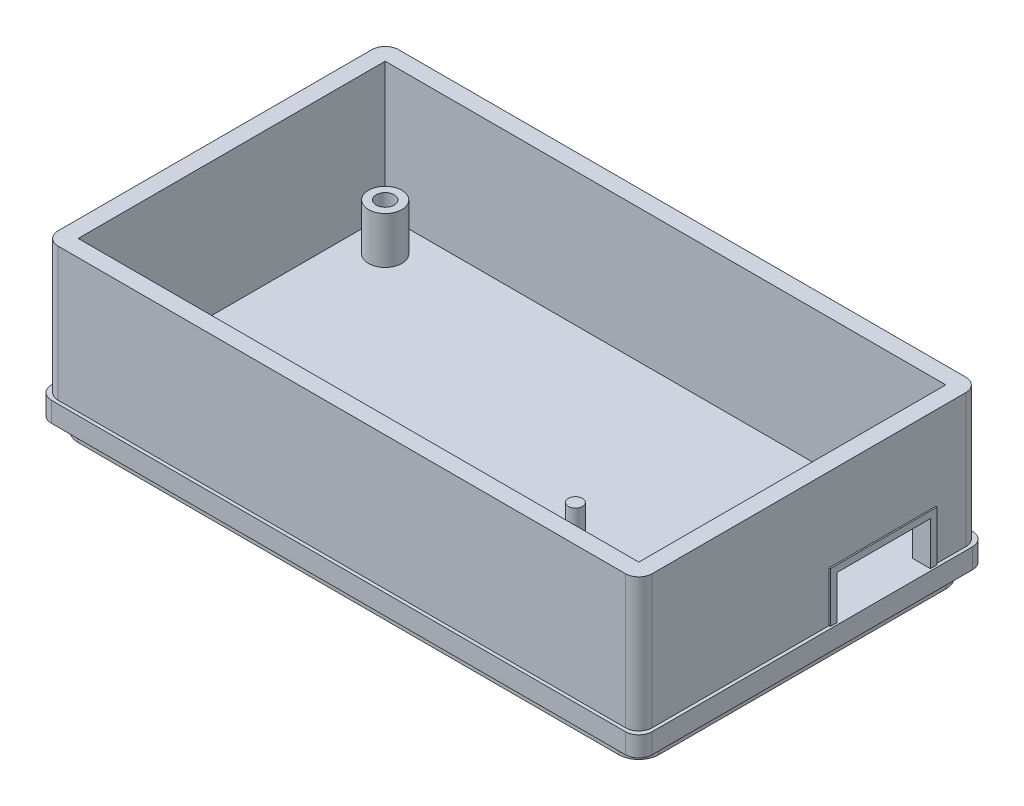
SolidWorks part; units mm, degrees
ref_plane "Front Plane" through (0, 0, 0) normal (0, 0, 1) x (1, 0, 0)
ref_plane "Top Plane" through (0, 0, 0) normal (0, 1, 0) x (1, 0, 0)
ref_plane "Right Plane" through (0, 0, 0) normal (1, 0, 0) x (0, 0, -1)
sketch "Sketch1" plane through (0, 0, 0) normal (0, 1, 0) x (1, 0, 0)
  line L1 (-45, 26) -> (45, 26)
  line L2 (-45, 26) -> (-45, -26)
  line L3 (-45, -26) -> (45, -26)
  line L4 (45, 26) -> (45, -26)
  dimension "D1" = 52
  dimension "D2" = 90
  dimension "D3" = 45
  dimension "D4" = 26
extrude "Boss-Extrude1" add sketch "Sketch1" along normal blind 3
sketch "Sketch3" plane through (0, 0, 0) normal (0, 1, 0) x (1, 0, 0)
  line L1 (-41.5, 22.5) -> (41.5, 22.5)
  line L2 (-41.5, 22.5) -> (-41.5, -22.5)
  line L3 (-41.5, -22.5) -> (41.5, -22.5)
  line L4 (41.5, 22.5) -> (41.5, -22.5)
  dimension "D1" = 45
  dimension "D2" = 83
  dimension "D3" = 41.5
  dimension "D4" = 22.5
sketch "Sketch4" plane through (0, 0, 0) normal (0, 1, 0) x (1, 0, 0)
  line L2 (-41.5, -22.5) -> (41.5, -22.5) construction
  line L3 (-41.5, 22.5) -> (-41.5, -22.5) construction
  circle A1 centre (29, -19.5) radius 2.5
  circle A2 centre (-37, 18) radius 2.5
  circle A3 centre (-37, -16.5) radius 2.5
  dimension "D4" = 5
  dimension "D5" = 3
  dimension "D8" = 4.5
  dimension "D9" = 6
extrude "Boss-Extrude2" add sketch "Sketch4" along normal blind 7 from surface starting at face at (0, 3, 0)
sketch "Sketch5" plane through (0, 0, 0) normal (0, 1, 0) x (1, 0, 0)
  circle A0 centre (-37, 18) radius 1.35
  circle A1 centre (-37, -16.5) radius 1.35
extrude "Cut-Extrude2" cut sketch "Sketch5" against normal through all both and the other way through all from surface starting at face at (-37, 10, -15.5)
sketch "Sketch6" plane through (0, 0, 0) normal (0, 1, 0) x (1, 0, 0)
  circle A0 centre (29, -19.5) radius 1.05
  dimension "D1" = 2.1
extrude "Boss-Extrude3" add sketch "Sketch6" along normal blind 12.5 from surface starting at face at (29, 10, 22)
sketch "Sketch7" plane through (0, 0, 0) normal (0, 1, 0) x (1, 0, 0)
  line L4 (40.5, 21.5) -> (-40.5, 21.5)
  line L5 (-40.5, 21.5) -> (-40.5, -21.5)
  line L6 (-40.5, -21.5) -> (40.5, -21.5)
  line L7 (40.5, -21.5) -> (40.5, 21.5)
  line L8 (43.5, 24.5) -> (-43.5, 24.5)
  line L9 (43.5, -24.5) -> (43.5, 24.5)
  line L10 (-43.5, -24.5) -> (43.5, -24.5)
  line L11 (-43.5, 24.5) -> (-43.5, -24.5)
  line L12 (43.5, 24.5) -> (-43.5, 24.5)
  line L13 (43.5, -24.5) -> (43.5, 24.5)
  line L14 (-43.5, -24.5) -> (43.5, -24.5)
  line L15 (-43.5, 24.5) -> (-43.5, -24.5)
  dimension "D1" = 2
  dimension "D2" = 3
extrude "Boss-Extrude4" add sketch "Sketch7" against normal blind 2
fillet "Fillet1" radius 3 4 edges at (-43.5, -1, 24.5) (-43.5, -1, -24.5) (43.5, -1, 24.5) (43.5, -1, -24.5)
sketch "Sketch8" plane through (0, 0, 0) normal (0, 1, 0) x (1, 0, 0)
  line L4 (44.5, 25.5) -> (-44.5, 25.5)
  line L5 (-44.5, 25.5) -> (-44.5, -25.5)
  line L6 (-44.5, -25.5) -> (44.5, -25.5)
  line L7 (44.5, -25.5) -> (44.5, 25.5)
  line L8 (42, 23) -> (-42, 23)
  line L9 (42, -23) -> (42, 23)
  line L10 (-42, -23) -> (42, -23)
  line L11 (-42, 23) -> (-42, -23)
  line L12 (42, 23) -> (-42, 23)
  line L13 (42, -23) -> (42, 23)
  line L14 (-42, -23) -> (42, -23)
  line L15 (-42, 23) -> (-42, -23)
  dimension "D1" = 0.5
  dimension "D2" = 2.5
extrude "Boss-Extrude8" add sketch "Sketch8" along normal blind 20 from surface starting at face at (29, 3, 22)
fillet "Fillet2" radius 2 8 edges at (-45, 1.5, 26) (-44.5, 13, 25.5) (-45, 1.5, -26) (-44.5, 13, -25.5) (45, 1.5, -26) (45, 1.5, 26) (44.5, 13, -25.5) (44.5, 13, 25.5)
sketch "Sketch9" plane through (0, 0, 0) normal (1, 0, 0) x (0, 0, -1)
  line L1 (4, 9.5) -> (18, 9.5)
  line L2 (4, 9.5) -> (4, 3)
  line L3 (4, 3) -> (18, 3)
  line L4 (18, 9.5) -> (18, 3)
  point P4 (0, 0)
  point P11 (0, 0)
  dimension "D1" = 14
  dimension "D2" = 6.5
  dimension "D4" = 5.5
extrude "Cut-Extrude3" cut sketch "Sketch9" along normal blind 15 from surface starting at face at (42, 13, 0)
sketch "Sketch10" plane through (0, 0, 0) normal (1, 0, 0) x (0, 0, -1)
  line L9 (18, 3) -> (18, 9.5)
  line L15 (18, 9.5) -> (4, 9.5)
  line L16 (4, 9.5) -> (4, 3)
  line L17 (19, 3) -> (19, 10.5)
  line L22 (3, 10.5) -> (3, 3)
  line L23 (19, 10.5) -> (3, 10.5)
  line L24 (19, 3) -> (19, 10.5)
  line L25 (3, 10.5) -> (3, 3)
  line L26 (19, 10.5) -> (3, 10.5)
  line L27 (3, 3) -> (4, 3)
  line L28 (18, 3) -> (19, 3)
  dimension "D2" = 1
  dimension "D1" = 1
extrude "Boss-Extrude9" add sketch "Sketch10" along normal blind 0.2 from surface starting at face at (44.5, 9.625, -5.5)
